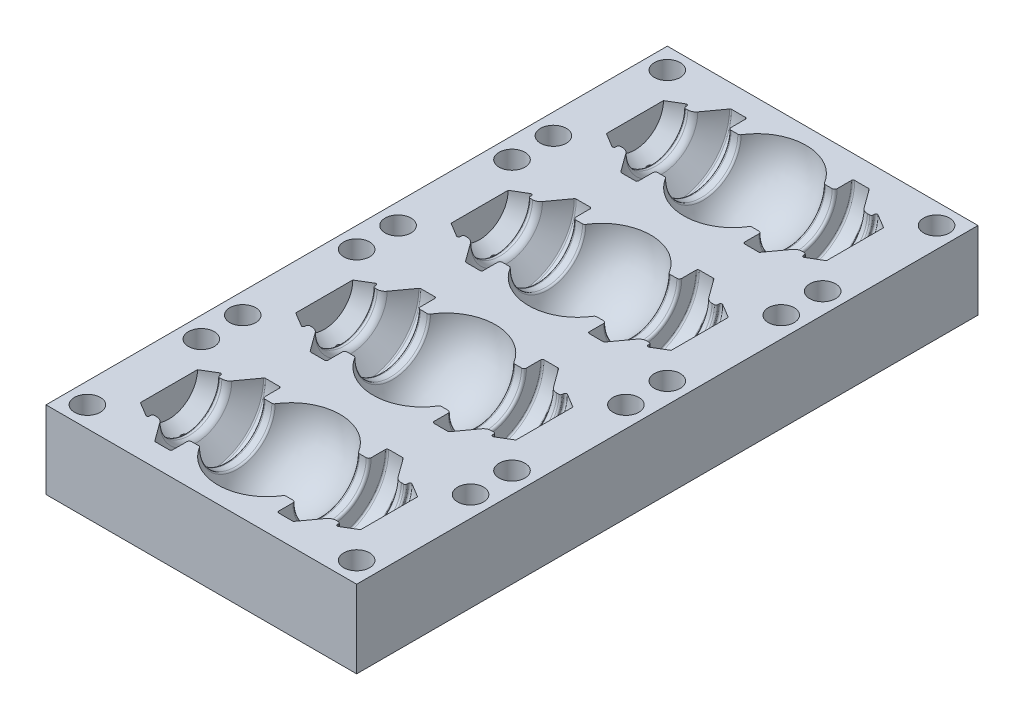
SolidWorks part; units mm, degrees
ref_plane "Front Plane" through (0, 0, 0) normal (0, 0, 1) x (1, 0, 0)
ref_plane "Top Plane" through (0, 0, 0) normal (0, 1, 0) x (1, 0, 0)
ref_plane "Right Plane" through (0, 0, 0) normal (1, 0, 0) x (0, 0, -1)
ref_axis "X - Axis" through (-88.99, 0, 0) along (1, 0, 0)
ref_axis "Y - Axis" through (0, 55, 0) along (0, -1, 0)
ref_axis "Z - Axis" through (0, 0, -88.99) along (0, 0, 1)
sketch "Sketch1" plane through (0, 0, 0) normal (0, 1, 0) x (1, 0, 0)
  line L1 (-19.05, 9.525) -> (19.05, 9.525)
  line L2 (-19.05, 9.525) -> (-19.05, -9.525)
  line L3 (-19.05, -9.525) -> (19.05, -9.525)
  line L4 (19.05, 9.525) -> (19.05, -9.525)
  line L5 (-19.05, 9.525) -> (19.05, -9.525) construction
  line L6 (-19.05, -9.525) -> (19.05, 9.525) construction
  point P0 (0, 0)
  dimension "D1" = 19.05
  dimension "D2" = 38.1
extrude "Boss-Extrude1" add sketch "Sketch1" against normal blind 9.525
sketch "Sketch2" plane through (0, 0, 0) normal (0, 1, 0) x (1, 0, 0)
  line L0 (-5.3703, 4.5) -> (-6.2, 4.5)
  line L1 (-6.7, 6.75) -> (-8.3982, 6.75)
  line L2 (-6.5, 4.8) -> (-6.5, 6.55)
  line L3 (-8.5599, 6.6676) -> (-10.2005, 4.4118)
  line L4 (-11.0092, 4) -> (-11.3, 4)
  line L5 (-11.5, 4.2) -> (-11.5, 4.3468)
  line L6 (-11.8029, 4.5183) -> (-13.5, 3.5)
  line L7 (0, 0) -> (0, 7.5) construction
  line L8 (-13.5, 0) -> (-13.5, 3.5)
  line L9 (-13.5, 0) -> (13.5, 0) construction
  line L10 (13.5, 3.5) -> (13.5, 0)
  line L11 (11.8029, 4.5183) -> (13.5, 3.5)
  line L12 (11.5, 4.2) -> (11.5, 4.3468)
  line L13 (11.0092, 4) -> (11.3, 4)
  line L14 (8.5599, 6.6676) -> (10.2005, 4.4118)
  line L15 (6.5, 4.8) -> (6.5, 6.55)
  line L16 (6.7, 6.75) -> (8.3982, 6.75)
  line L17 (5.3703, 4.5) -> (6.2, 4.5)
  line L18 (19.05, -9.525) -> (19.05, 9.525) construction
  line L19 (19.05, 9.525) -> (-19.05, 9.525) construction
  line L20 (-13.5, 0) -> (13.5, 0)
  arc A0 (5.1148, 4.6427) -> (-5.1148, 4.6427) centre (0, 1.4933) ccw
  arc A1 (-5.3703, 4.5) -> (-5.1148, 4.6427) centre (-5.3703, 4.8) ccw
  arc A2 (-6.5, 4.8) -> (-6.2, 4.5) centre (-6.2, 4.8) ccw
  arc A3 (-6.5, 6.55) -> (-6.7, 6.75) centre (-6.7, 6.55) ccw
  arc A4 (-8.3982, 6.75) -> (-8.5599, 6.6676) centre (-8.3982, 6.55) ccw
  arc A5 (-11.0092, 4) -> (-10.2005, 4.4118) centre (-11.0092, 5) ccw
  arc A6 (-11.5, 4.2) -> (-11.3, 4) centre (-11.3, 4.2) ccw
  arc A7 (-11.5, 4.3468) -> (-11.8029, 4.5183) centre (-11.7, 4.3468) ccw
  arc A8 (11.5, 4.3468) -> (11.8029, 4.5183) centre (11.7, 4.3468) cw
  arc A9 (11.5, 4.2) -> (11.3, 4) centre (11.3, 4.2) cw
  arc A10 (11.0092, 4) -> (10.2005, 4.4118) centre (11.0092, 5) cw
  arc A11 (8.3982, 6.75) -> (8.5599, 6.6676) centre (8.3982, 6.55) cw
  arc A12 (6.5, 6.55) -> (6.7, 6.75) centre (6.7, 6.55) cw
  arc A13 (6.5, 4.8) -> (6.2, 4.5) centre (6.2, 4.8) cw
  arc A14 (5.3703, 4.5) -> (5.1148, 4.6427) centre (5.3703, 4.8) cw
  point P93 (13.5, 0)
  dimension "D1" = 6.0067
  dimension "D2" = 0.3
  dimension "D3" = 0.2
  dimension "D4" = 1
  dimension "D5" = 5.55
  dimension "D6" = 7.2471
  dimension "D7" = 7.35
  dimension "D8" = 8.0408
  dimension "D9" = 8.8495
  dimension "D10" = 10.4901
  dimension "D11" = 12.55
  dimension "D12" = 13.6797
  dimension "D13" = 2.775
  dimension "D14" = 4.8823
  dimension "D15" = 5.0067
revolve "Cut-Revolve1" cut sketch "Sketch2" angle 360 about L20
hole_wizard "1/8 (0.125) Diameter Hole1" positions "Sketch7" profile "Sketch6" hole size "1/8" standard "ANSI Inch"
sketch "Sketch7" plane through (0, 0, 0) normal (0, 1, 0) x (1, 0, 0)
  line L1 (-16.51, 6.985) -> (16.51, 6.985)
  line L2 (-16.51, 6.985) -> (-16.51, -6.985)
  line L3 (-16.51, -6.985) -> (16.51, -6.985)
  line L4 (16.51, 6.985) -> (16.51, -6.985)
  line L5 (-16.51, 6.985) -> (16.51, -6.985) construction
  line L6 (-16.51, -6.985) -> (16.51, 6.985) construction
  line L7 (19.05, 9.525) -> (-19.05, 9.525) construction
  line L8 (-19.05, 9.525) -> (-19.05, -9.525) construction
  point P0 (-16.51, 6.985)
  point P2 (16.51, -6.985)
  point P4 (16.51, 6.985)
  point P6 (-16.51, -6.985)
  point P70 (0, 0)
  dimension "D1" = 2.54
  dimension "D2" = 2.54
sketch "Sketch6" plane through (-16.51, 0, -6.985) normal (1, 0, 0) x (0, 0, 1)
  line L0 (0, 0) -> (0, 7.3039)
  line L1 (0, 7.3039) -> (1.5875, 6.35)
  line L2 (1.5875, 6.35) -> (1.5875, 0)
  line L5 (1.5875, 0) -> (0, 0)
  line L10 (0, 7.3039) -> (-1.5875, 6.35) construction
  line L11 (0, -6.35) -> (0, 107.95) construction
  dimension "Hole Dia." = 3.175
  dimension "Hole Depth" = 6.35
  dimension "Drill Angle" = 118
sketch "Sketch8" plane through (-19.05, 0, 0) normal (-1, 0, 0) x (0, 0, 1)
  line L0 (-9.525, 0) -> (9.525, 0) construction
  circle A0 centre (0, 0) radius 1.5875
  dimension "D1" = 3.175
extrude "Cut-Extrude1" [suppressed] cut sketch "Sketch8" against normal through all
sketch "Sketch9" plane through (0, -9.525, 0) normal (0, -1, 0) x (1, 0, 0)
  line L0 (-8.3982, 0) -> (-6.7, 0) construction
  line L1 (-8.3982, -6.75) -> (-8.3982, 6.75) construction
  line L2 (-6.7, -6.75) -> (-6.7, 6.75) construction
  line L4 (-11.8029, 0) -> (-11.5, 0) construction
  line L5 (-11.8029, -4.5183) -> (-11.8029, 4.5183) construction
  line L6 (-11.5, 4.3468) -> (-11.5, -4.3468) construction
  line L7 (6.7, 0) -> (8.3982, 0) construction
  line L8 (6.7, -6.75) -> (6.7, 6.75) construction
  line L9 (8.3982, -6.75) -> (8.3982, 6.75) construction
  line L10 (11.5, 0) -> (11.8029, 0) construction
  line L11 (11.5, -4.3468) -> (11.5, 4.3468) construction
  line L12 (11.8029, -4.5183) -> (11.8029, 4.5183) construction
  circle A0 centre (-7.5491, 0) radius 0.4064
  circle A1 centre (0, 0) radius 0.4064
  circle A2 centre (7.5491, 0) radius 0.4064
  circle A3 centre (11.6514, 0) radius 0.4064
  circle A4 centre (-11.6514, 0) radius 0.4064
  circle A5 centre (0, 6.35) radius 0.635
  dimension "D1" = 0.8128
  dimension "D3" = 1.27
  dimension "D2" = 6.35
sketch "Sketch10" plane through (0, -9.525, 0) normal (0, -1, 0) x (1, 0, 0)
  circle A0 centre (-7.5491, 0) radius 0.4064 construction
  circle A1 centre (0, 0) radius 0.4064 construction
  circle A2 centre (0, 6.35) radius 0.635 construction
  circle A3 centre (7.5491, 0) radius 0.4064 construction
  circle A5 centre (-7.5491, 0) radius 0.4064
  circle A6 centre (0, 0) radius 0.4064
  circle A7 centre (0, 6.35) radius 0.635
  circle A8 centre (7.5491, 0) radius 0.4064
hole_wizard " (0.04688) Diameter Hole1" positions "Sketch12" profile "Sketch11" hole size "3/64" standard "ANSI Inch"
sketch "Sketch12" plane through (0, -9.525, 0) normal (0, -1, 0) x (-1, 0, 0)
  point P0 (11.6514, 0)
  point P3 (-11.6514, 0)
sketch "Sketch11" plane through (-11.6514, -9.525, 0) normal (1, 0, 0) x (0, 0, -1)
  line L0 (0, 0) -> (0, 5.3107)
  line L1 (0, 5.3107) -> (0.5954, 4.953)
  line L2 (0.5954, 4.953) -> (0.5954, 0)
  line L5 (0.5954, 0) -> (0, 0)
  line L10 (0, 5.3107) -> (-0.5954, 4.953) construction
  line L11 (0, -6.35) -> (0, 107.95) construction
  dimension "Hole Dia." = 1.1908
  dimension "Hole Depth" = 4.953
  dimension "Drill Angle" = 118
hole_wizard "7/64 (0.10938) Diameter Hole1" positions "Sketch15" profile "Sketch14" hole size "7/64" standard "ANSI Inch"
sketch "Sketch15" plane through (0, -9.525, 0) normal (0, -1, 0) x (-1, 0, 0)
  point P0 (0, -6.35)
sketch "Sketch14" plane through (0, -9.525, 6.35) normal (1, 0, 0) x (0, 0, -1)
  line L0 (0, 0) -> (0, 3.2477)
  line L1 (0, 3.2477) -> (1.3891, 2.413)
  line L2 (1.3891, 2.413) -> (1.3891, 0)
  line L5 (1.3891, 0) -> (0, 0)
  line L10 (0, 3.2477) -> (-1.3891, 2.413) construction
  line L11 (0, -6.35) -> (0, 107.95) construction
  dimension "Hole Dia." = 2.7783
  dimension "Hole Depth" = 2.413
  dimension "Drill Angle" = 118
hole_wizard "3/64 (0.04688) Diameter Hole2" positions "Sketch17" profile "Sketch16" hole size "3/64" standard "ANSI Inch"
sketch "Sketch17" plane through (0, -9.525, 0) normal (0, -1, 0) x (-1, 0, 0)
  point P0 (0, 0)
sketch "Sketch16" plane through (0, -9.525, 0) normal (1, 0, 0) x (0, 0, -1)
  line L0 (0, 0) -> (0, 2.2627)
  line L1 (0, 2.2627) -> (0.5954, 1.905)
  line L2 (0.5954, 1.905) -> (0.5954, 0)
  line L5 (0.5954, 0) -> (0, 0)
  line L10 (0, 2.2627) -> (-0.5954, 1.905) construction
  line L11 (0, -6.35) -> (0, 107.95) construction
  dimension "Hole Dia." = 1.1908
  dimension "Hole Depth" = 1.905
  dimension "Drill Angle" = 118
hole_wizard "3/64 (0.04688) Diameter Hole3" positions "Sketch19" profile "Sketch18" hole size "3/64" standard "ANSI Inch"
sketch "Sketch19" plane through (0, -9.525, 0) normal (0, -1, 0) x (-1, 0, 0)
  point P0 (-7.5491, 0)
  point P3 (7.5491, 0)
sketch "Sketch18" plane through (7.5491, -9.525, 0) normal (1, 0, 0) x (0, 0, -1)
  line L0 (0, 0) -> (0, 3.0247)
  line L1 (0, 3.0247) -> (0.5954, 2.667)
  line L2 (0.5954, 2.667) -> (0.5954, 0)
  line L5 (0.5954, 0) -> (0, 0)
  line L10 (0, 3.0247) -> (-0.5954, 2.667) construction
  line L11 (0, -6.35) -> (0, 107.95) construction
  dimension "Hole Dia." = 1.1908
  dimension "Hole Depth" = 2.667
  dimension "Drill Angle" = 118
hole_wizard "1/16 (0.0625) Diameter Hole1" positions "Sketch21" profile "Sketch20" hole size "1/16" standard "ANSI Inch"
sketch "Sketch21" plane through (0, -9.525, 0) normal (0, -1, 0) x (-1, 0, 0)
  point P0 (0, -6.35)
sketch "Sketch20" plane through (0, -9.525, 6.35) normal (1, 0, 0) x (0, 0, -1)
  line L0 (0, 0) -> (0, 5.6839)
  line L1 (0, 5.6839) -> (0.7937, 5.207)
  line L2 (0.7937, 5.207) -> (0.7937, 0)
  line L5 (0.7937, 0) -> (0, 0)
  line L10 (0, 5.6839) -> (-0.7938, 5.207) construction
  line L11 (0, -6.35) -> (0, 107.95) construction
  dimension "Hole Dia." = 1.5875
  dimension "Hole Depth" = 5.207
  dimension "Drill Angle" = 118
pattern_linear "LPattern1" [suppressed] count 4 spacing 19.05 of bodies 106
pattern_linear "LPattern2" count 4 spacing 19.05 along (0, 0, -1) of "1/8 (0.125) Diameter Hole1", "Cut-Revolve1", "Boss-Extrude1"
pattern_linear "LPattern3" count 4 spacing 19.05 along (0, 0, -1) of " (0.04688) Diameter Hole1", "7/64 (0.10938) Diameter Hole1", "3/64 (0.04688) Diameter Hole2", "3/64 (0.04688) Diameter Hole3", "1/16 (0.0625) Diameter Hole1"
